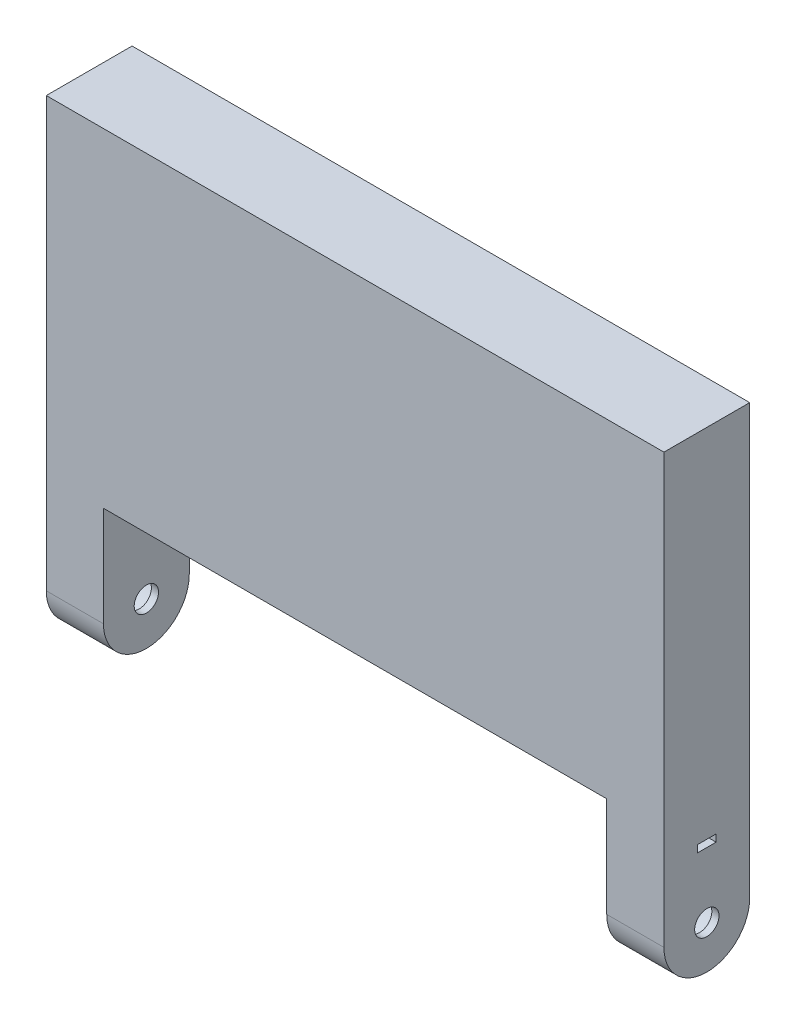
SolidWorks part; units mm, degrees
ref_plane "Front Plane" through (0, 0, 0) normal (0, 0, 1) x (1, 0, 0)
ref_plane "Top Plane" through (0, 0, 0) normal (0, 1, 0) x (1, 0, 0)
ref_plane "Right Plane" through (0, 0, 0) normal (1, 0, 0) x (0, 0, -1)
sketch "Sketch1" plane through (0, 0, 0) normal (0, 0, 1) x (1, 0, 0)
  line L0 (-276.0597, 0) -> (276.0597, 0) construction
  line L1 (-216, -30) -> (-216, 300)
  line L2 (-216, 300) -> (0, 300)
  line L3 (-216, -30) -> (-176, -30)
  line L4 (0, -283.5322) -> (0, 283.5322) construction
  line L5 (-176, -30) -> (-176, 70)
  line L6 (-176, 70) -> (0, 70)
  line L7 (-238.394, -30) -> (238.394, -30) construction
  line L8 (-181, 75) -> (0, 75)
  line L9 (-181, -25) -> (-181, 75)
  line L10 (-211, -25) -> (-181, -25)
  line L11 (-211, -25) -> (-211, 295)
  line L12 (-211, 295) -> (0, 295)
  point P10 (0, -30)
  dimension "D1" = 432
  dimension "D2" = 100
  dimension "D3" = 60
  dimension "D4" = 300
  dimension "D5" = 352
  dimension "D6" = 5
sketch "Sketch3" plane through (0, 0, 0) normal (1, 0, 0) x (0, 0, -1)
  line L0 (0, 0) -> (0, -30) construction
  line L1 (0, -283.5322) -> (0, 283.5322) construction
  line L2 (-30, 0) -> (-30, 300)
  line L3 (-30, 300) -> (30, 300)
  line L4 (30, 300) -> (30, 0)
  line L5 (30, 70) -> (-30, 70)
  line L6 (25, 295) -> (25, 0)
  line L7 (-25, 0) -> (-25, 295)
  line L8 (-25, 295) -> (25, 295)
  line L9 (30, 75) -> (-30, 75)
  line L11 (6.5, 50.5) -> (-6.5, 50.5)
  line L12 (6.5, 50.5) -> (6.5, 45.5)
  line L13 (6.5, 45.5) -> (-6.5, 45.5)
  line L14 (-6.5, 50.5) -> (-6.5, 45.5)
  line L15 (6.5, 50.5) -> (-6.5, 45.5) construction
  line L16 (6.5, 45.5) -> (-6.5, 50.5) construction
  arc A0 (-30, 0) -> (30, 0) centre (0, 0) ccw
  arc A1 (-25, 0) -> (25, 0) centre (0, 0) ccw
  point P21 (0, 48)
  point P26 (0, 0)
  dimension "D2" = 5
  dimension "D3" = 13
  dimension "D4" = 5
  dimension "D5" = 78
  dimension "D1" = 5
extrude "Boss-Extrude1" add sketch "Sketch3" along normal up to vertex (-211 mm away) from vertex contours L9 L6 L8 L7 | L9 L4 L3 L2 L7 L8 L6 | L6 L9 L7 L5 | L4 L9 L6 L5 | L7 L9 L2 L5 | L0 A1 L7 L5 L2 A0 | A1 L0 A0 L4 L5 L6 | L7 A1 L6 L5 region at (0, 35, 28.8338) region at (0, 72.5, 27.5) region at (0, 187.5, 27.6714) region at (0, 72.5, 0) region at (0, 24.6705, 0) region at (0, 72.5, -27.5) region at (0, 185, 0) up to point (-211, -25, 0) starting at point (-216, -30, 0)
extrude "Boss-Extrude2" add sketch "Sketch3<4>" along normal up to vertex (-181 mm away) from vertex contours L9 L4 L3 L2 L7 L8 L6 | A1 L7 L5 L2 A0 L4 L6 | L7 L9 L2 L5 | L4 L9 L6 L5 region at (0, 35, 28.8338) region at (0, 72.5, 27.5) region at (0, 187.5, 27.6714) region at (0, 72.5, -27.5) up to point (-181, -25, 0) starting at point (-211, -25, 0)
sketch "Sketch3<4>" plane through (0, 0, 0) normal (1, 0, 0) x (0, 0, -1) same geometry as "Sketch3"
extrude "Boss-Extrude3" add sketch "Sketch3<5>" along normal up to vertex (-176 mm away) from vertex contours L9 L4 L3 L2 L7 L8 L6 | L7 L9 L2 L5 | L4 L9 L6 L5 | L6 L9 L7 L5 | A1 L0 A0 L4 L5 L6 | L7 A1 L6 L5 | L0 A1 L7 L5 L2 A0 | L11 L14 L13 L12 region at (0, 35, 28.8338) region at (0, 72.5, 27.5) region at (0, 187.5, 27.6714) region at (0, 72.5, 0) region at (0, 24.6705, 0) region at (0, 72.5, -27.5) region at (0, 48, 0) up to point (-176, -30, 0) starting at point (-181, -25, 0)
sketch "Sketch3<5>" plane through (0, 0, 0) normal (1, 0, 0) x (0, 0, -1) same geometry as "Sketch3"
extrude "Boss-Extrude4" add sketch "Sketch3<6>" along normal up to surface from vertex contours L9 L4 L3 L2 L7 L8 L6 | L7 L9 L2 L5 | L6 L9 L7 L5 | L4 L9 L6 L5 region at (0, 72.5, 27.5) region at (0, 187.5, 27.6714) region at (0, 72.5, 0) region at (0, 72.5, -27.5) up to plane "Right Plane" starting at point (-176, 70, 0)
sketch "Sketch3<6>" plane through (0, 0, 0) normal (1, 0, 0) x (0, 0, -1) same geometry as "Sketch3"
sketch "Sketch6" plane through (0, 0, 0) normal (1, 0, 0) x (0, 0, -1)
  line L0 (0, -283.5322) -> (0, 283.5322) construction
  circle A0 centre (0, 0) radius 8.5
  dimension "D1" = 17
extrude "Cut-Extrude1" cut sketch "Sketch6" against normal through all
mirror "Mirror5" about plane through (0, 0, 0) normal (1, 0, 0) of bodies 108 104
equation "\"D2@Sketch3\"=\"D1@Sketch3\""
